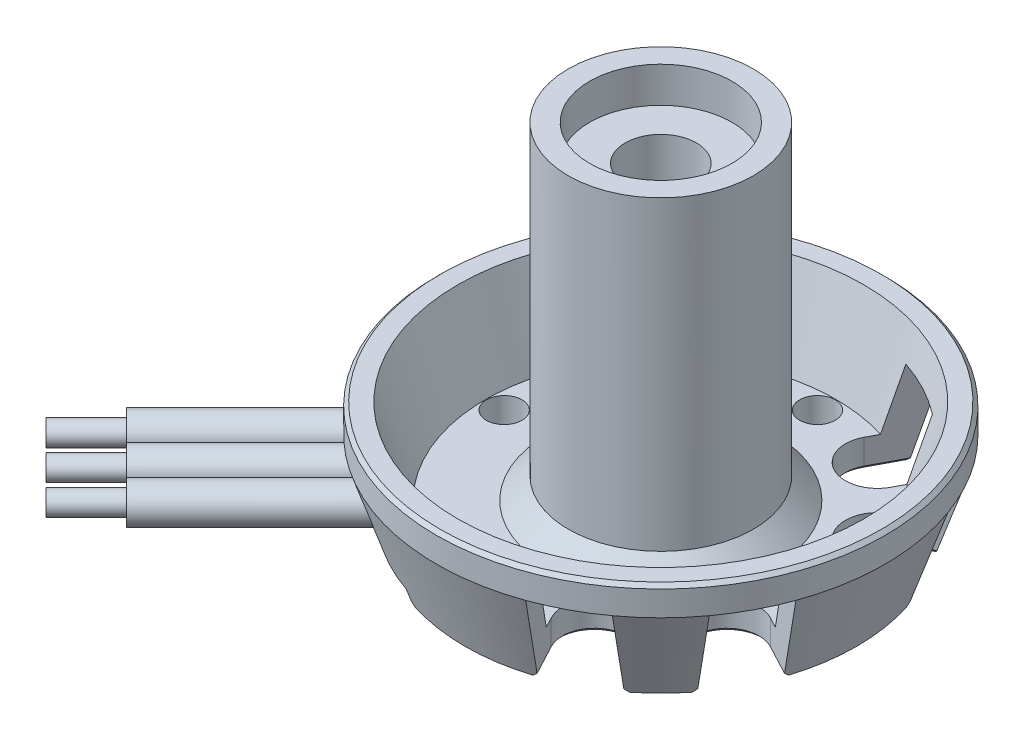
SolidWorks part; units mm, degrees
material "7075-T6，板材(SS)"
ref_plane "前视基准面" through (0, 0, 0) normal (0, 0, 1) x (1, 0, 0)
ref_plane "上视基准面" through (0, 0, 0) normal (0, 1, 0) x (1, 0, 0)
ref_plane "右视基准面" through (0, 0, 0) normal (1, 0, 0) x (0, 0, -1)
sketch "草图3" plane through (0, 0, 0) normal (0, 1, 0) x (1, 0, 0)
  circle A0 centre (0, 0) radius 31.5
  dimension "D1" = 63
extrude "凸台-拉伸1" add sketch "草图3" along normal blind 81
sketch "草图4" plane through (0, 0, 0) normal (0, -1, 0) x (1, 0, 0)
  line L0 (0, 0) -> (31.5, 0) construction
  line L1 (10.5631, 19.8663) -> (0, 0) construction
  line L2 (0, 0) -> (0, 31.5) construction
  line L3 (0, 0) -> (22.2739, 22.2739) construction
  line L4 (10.5631, 19.8663) -> (14.7884, 27.8128) construction
  line L5 (6.5898, 21.9789) -> (10.8151, 29.9255)
  line L6 (14.5364, 17.7537) -> (18.7616, 25.7002)
  line L7 (19.8663, 10.5631) -> (27.8128, 14.7884) construction
  line L8 (21.9789, 6.5898) -> (29.9255, 10.8151)
  line L9 (17.7537, 14.5364) -> (25.7002, 18.7616)
  line L10 (-10.5631, 19.8663) -> (-14.7884, 27.8128) construction
  line L11 (-6.5898, 21.9789) -> (-10.8151, 29.9255)
  line L12 (-14.5364, 17.7537) -> (-18.7616, 25.7002)
  line L13 (-19.8663, 10.5631) -> (-27.8128, 14.7884) construction
  line L14 (-21.9789, 6.5898) -> (-29.9255, 10.8151)
  line L15 (-17.7537, 14.5364) -> (-25.7002, 18.7616)
  line L16 (10.5631, -19.8663) -> (14.7884, -27.8128) construction
  line L17 (6.5898, -21.9789) -> (10.8151, -29.9255)
  line L18 (14.5364, -17.7537) -> (18.7616, -25.7002)
  line L19 (19.8663, -10.5631) -> (27.8128, -14.7884) construction
  line L20 (21.9789, -6.5898) -> (29.9255, -10.8151)
  line L21 (17.7537, -14.5364) -> (25.7002, -18.7616)
  line L22 (-10.5631, -19.8663) -> (-14.7884, -27.8128) construction
  line L23 (-6.5898, -21.9789) -> (-10.8151, -29.9255)
  line L24 (-14.5364, -17.7537) -> (-18.7616, -25.7002)
  line L25 (-19.8663, -10.5631) -> (-27.8128, -14.7884) construction
  line L26 (-21.9789, -6.5898) -> (-29.9255, -10.8151)
  line L27 (-17.7537, -14.5364) -> (-25.7002, -18.7616)
  circle A0 centre (0, 0) radius 22 construction
  arc A1 (21.9789, 6.5898) -> (17.7537, 14.5364) centre (19.8663, 10.5631) cw
  circle A2 centre (0, 0) radius 31.5 construction
  arc A3 (25.7002, 18.7616) -> (29.9255, 10.8151) centre (27.8128, 14.7884) cw
  arc A4 (6.5898, 21.9789) -> (14.5364, 17.7537) centre (10.5631, 19.8663) ccw
  arc A5 (18.7616, 25.7002) -> (10.8151, 29.9255) centre (14.7884, 27.8128) ccw
  arc A6 (-6.5898, 21.9789) -> (-14.5364, 17.7537) centre (-10.5631, 19.8663) cw
  arc A7 (-18.7616, 25.7002) -> (-10.8151, 29.9255) centre (-14.7884, 27.8128) cw
  arc A8 (-21.9789, 6.5898) -> (-17.7537, 14.5364) centre (-19.8663, 10.5631) ccw
  arc A9 (-25.7002, 18.7616) -> (-29.9255, 10.8151) centre (-27.8128, 14.7884) ccw
  arc A10 (6.5898, -21.9789) -> (14.5364, -17.7537) centre (10.5631, -19.8663) cw
  arc A11 (18.7616, -25.7002) -> (10.8151, -29.9255) centre (14.7884, -27.8128) cw
  arc A12 (21.9789, -6.5898) -> (17.7537, -14.5364) centre (19.8663, -10.5631) ccw
  arc A13 (25.7002, -18.7616) -> (29.9255, -10.8151) centre (27.8128, -14.7884) ccw
  arc A14 (-6.5898, -21.9789) -> (-14.5364, -17.7537) centre (-10.5631, -19.8663) ccw
  arc A15 (-18.7616, -25.7002) -> (-10.8151, -29.9255) centre (-14.7884, -27.8128) ccw
  arc A16 (-21.9789, -6.5898) -> (-17.7537, -14.5364) centre (-19.8663, -10.5631) cw
  arc A17 (-25.7002, -18.7616) -> (-29.9255, -10.8151) centre (-27.8128, -14.7884) cw
  circle A18 centre (0, 22) radius 2.5
  circle A19 centre (0, -22) radius 2.5
  circle A20 centre (-22, 0) radius 2.5
  circle A21 centre (22, 0) radius 2.5
  point P13 (12.6757, 23.8396)
  point P19 (23.8396, 12.6757)
  point P26 (-12.6757, 23.8396)
  point P33 (-23.8396, 12.6757)
  point P40 (12.6757, -23.8396)
  point P47 (23.8396, -12.6757)
  point P54 (-12.6757, -23.8396)
  point P61 (-23.8396, -12.6757)
  dimension "D1" = 44
  dimension "D2" = 22.5
  dimension "D6" = 5
  dimension "D3" = 28
  dimension "D4" = 9
  dimension "D5" = 45
extrude "切除-拉伸1" cut sketch "草图4" against normal blind 2
sketch "草图5" plane through (0, 0, 0) normal (0, -1, 0) x (1, 0, 0)
  circle A0 centre (0, 0) radius 9
  dimension "D1" = 18
extrude "切除-拉伸2" cut sketch "草图5" against normal blind 1.2
sketch "草图6" plane through (0, 1.2, 0) normal (0, -1, 0) x (1, 0, 0)
  circle A0 centre (0, 0) radius 5
  dimension "D1" = 10
extrude "凸台-拉伸2" add sketch "草图6" along normal blind 40
ref_plane "基准面1" through (-9.2322, 0, 9.2322) normal (-0.7071, 0, 0.7071) x (0.7071, 0, 0.7071)
sketch "草图9" plane through (0, 0, 0) normal (1, 0, 0) x (0, 0, -1)
  line L0 (-31.5, 0) -> (-31.5, -3.75)
  line L1 (-31.5, 81) -> (-31.5, 0) construction
  line L2 (-31.5, -3.75) -> (-35.25, 0)
  line L3 (-25.415, 0) -> (-18.6099, 0) construction
  line L4 (-35.25, 0) -> (-31.5, 0)
  line L5 (0, 0) -> (0, 10.6937) construction
  line L6 (-31.5, 81) -> (-31.5, 0) construction
  line L7 (-31.5, 16.5) -> (-30.5, 16.5)
  line L8 (-31.5, 16.5) -> (-31.5, 16)
  line L9 (-31.5, 16) -> (-30.5, 16)
  line L10 (-30.5, 16.5) -> (-30.5, 16)
  line L11 (-31.5, 81) -> (-31.5, 0) construction
  dimension "D1" = 45
  dimension "D2" = 35.25
  dimension "D3" = 0.5
  dimension "D4" = 16
  dimension "D5" = 1
revolve "切除-旋转1" cut sketch "草图9" angle 360 about L5
chamfer "倒角1" distance 1.2 angle 45 1 edges at (0, 1.2, -9)
sketch "草图11" plane through (0, 2, 0) normal (0, -1, 0) x (1, 0, 0)
  line L0 (14.5364, 17.7537) -> (18.6099, 25.415) construction
  line L1 (10.6634, 29.6402) -> (6.5898, 21.9789) construction
  line L2 (25.415, 18.6099) -> (17.7537, 14.5364) construction
  line L3 (21.9789, 6.5898) -> (29.6402, 10.6634) construction
  line L4 (17.7537, -14.5364) -> (25.415, -18.6099) construction
  line L5 (29.6402, -10.6634) -> (21.9789, -6.5898) construction
  line L6 (18.6099, -25.415) -> (14.5364, -17.7537) construction
  line L7 (6.5898, -21.9789) -> (10.6634, -29.6402) construction
  line L8 (-14.5364, -17.7537) -> (-18.6099, -25.415) construction
  line L9 (-10.6634, -29.6402) -> (-6.5898, -21.9789) construction
  line L10 (-25.415, -18.6099) -> (-17.7537, -14.5364) construction
  line L11 (-21.9789, -6.5898) -> (-29.6402, -10.6634) construction
  line L12 (14.5364, 17.7537) -> (22.5148, 32.7589)
  line L13 (14.5683, 36.9842) -> (6.5898, 21.9789)
  line L14 (32.7589, 22.5148) -> (17.7537, 14.5364)
  line L15 (21.9789, 6.5898) -> (36.9842, 14.5683)
  line L16 (17.7537, -14.5364) -> (32.7589, -22.5148)
  line L17 (36.9842, -14.5683) -> (21.9789, -6.5898)
  line L18 (22.5148, -32.7589) -> (14.5364, -17.7537)
  line L19 (6.5898, -21.9789) -> (14.5683, -36.9842)
  line L20 (-14.5364, -17.7537) -> (-22.5148, -32.7589)
  line L21 (-14.5683, -36.9842) -> (-6.5898, -21.9789)
  line L22 (-32.7589, -22.5148) -> (-17.7537, -14.5364)
  line L23 (-21.9789, -6.5898) -> (-36.9842, -14.5683)
  arc A1 (6.5898, 21.9789) -> (14.5364, 17.7537) centre (10.5631, 19.8663) ccw construction
  arc A3 (17.7537, 14.5364) -> (21.9789, 6.5898) centre (19.8663, 10.5631) ccw construction
  arc A5 (21.9789, -6.5898) -> (17.7537, -14.5364) centre (19.8663, -10.5631) ccw construction
  arc A7 (14.5364, -17.7537) -> (6.5898, -21.9789) centre (10.5631, -19.8663) ccw construction
  arc A9 (-6.5898, -21.9789) -> (-14.5364, -17.7537) centre (-10.5631, -19.8663) ccw construction
  arc A11 (-17.7537, -14.5364) -> (-21.9789, -6.5898) centre (-19.8663, -10.5631) ccw construction
  circle A12 centre (22, 0) radius 2.5 construction
  arc A13 (6.5898, 21.9789) -> (14.5364, 17.7537) centre (10.5631, 19.8663) ccw
  circle A14 centre (0, -22) radius 2.5 construction
  arc A15 (17.7537, 14.5364) -> (21.9789, 6.5898) centre (19.8663, 10.5631) ccw
  circle A16 centre (-22, 0) radius 2.5 construction
  arc A17 (21.9789, -6.5898) -> (17.7537, -14.5364) centre (19.8663, -10.5631) ccw
  circle A18 centre (0, 22) radius 2.5 construction
  arc A19 (14.5364, -17.7537) -> (6.5898, -21.9789) centre (10.5631, -19.8663) ccw
  circle A20 centre (22, 0) radius 2.5
  arc A21 (-6.5898, -21.9789) -> (-14.5364, -17.7537) centre (-10.5631, -19.8663) ccw
  circle A22 centre (0, -22) radius 2.5
  arc A23 (-17.7537, -14.5364) -> (-21.9789, -6.5898) centre (-19.8663, -10.5631) ccw
  arc A25 (-36.9842, -14.5683) -> (-32.7589, -22.5148) centre (0, 0) ccw
  arc A26 (-22.5148, -32.7589) -> (-14.5683, -36.9842) centre (0, 0) ccw
  arc A27 (14.5683, -36.9842) -> (22.5148, -32.7589) centre (0, 0) ccw
  arc A28 (32.7589, -22.5148) -> (36.9842, -14.5683) centre (0, 0) ccw
  arc A29 (36.9842, 14.5683) -> (32.7589, 22.5148) centre (0, 0) ccw
  arc A30 (22.5148, 32.7589) -> (14.5683, 36.9842) centre (0, 0) ccw
  circle A31 centre (-22, 0) radius 2.5
  circle A32 centre (0, 22) radius 2.5
  dimension "D1" = 39.75
extrude "切除-拉伸3" cut sketch "草图11" against normal offset from surface (10 mm away) 12 up to face at (0, 0, -9)
sketch "Sketch2" plane through (0, 0, 0) normal (0, 0, 1) x (1, 0, 0)
  line L0 (31.5, 12) -> (31.5, 0)
  line L2 (31.5, 0) -> (27.5, 0)
  line L3 (21.9789, 0) -> (29.6402, 0) construction
  line L4 (27.5, 0) -> (31.5, 12)
  line L5 (25.415, 12) -> (29.6402, 12) construction
  line L6 (0, 0) -> (0, -6.7384) construction
  line L7 (25.415, 12) -> (29.6402, 12) construction
  line L8 (31.5, 0) -> (31.5, 16) construction
  dimension "D1" = 4
revolve "Cut-Revolve1" cut sketch "Sketch2" angle 360 about L6
sketch "草图12" plane through (0, 16, 0) normal (0, 1, 0) x (1, 0, 0)
  circle A1 centre (0, 0) radius 31.5
  circle A2 centre (0, 0) radius 31.5
  dimension "D1" = 0
extrude "切除-拉伸4" cut sketch "草图12" along normal through all
sketch "草图13" plane through (0, -38.8, 0) normal (0, -1, 0) x (1, 0, 0)
  circle A1 centre (0, 0) radius 5
  circle A2 centre (0, 0) radius 5
  dimension "D1" = 0
extrude "切除-拉伸5" cut sketch "草图13" against normal through all
sketch "草图8" plane through (-9.2322, 0, 9.2322) normal (-0.7071, 0, 0.7071) x (0.7071, 0, 0.7071)
  line L0 (-31.5, 0) -> (28.499, 0) construction
  line L1 (0, 8) -> (0, 0) construction
  circle A0 centre (0, 8) radius 2.5
  circle A1 centre (6, 8) radius 2.5
  circle A2 centre (-6, 8) radius 2.5
  point P10 (0, 0)
  dimension "D1" = 5
  dimension "D2" = 8
  dimension "D4" = 6
  dimension "D3" = 2
extrude "凸台-拉伸3" add sketch "草图8" along normal blind 40
sketch "草图15" plane through (0, 16, 0) normal (0, 1, 0) x (1, 0, 0)
  circle A0 centre (0, 0) radius 28.5
  circle A1 centre (0, 0) radius 31.5
  circle A2 centre (0, 0) radius 31.5 construction
  dimension "D1" = 0
  dimension "D2" = 3
extrude "切除-拉伸6" cut sketch "草图15" against normal offset from surface 8 draft 18
sketch "草图16" plane through (0, 4, 0) normal (0, 1, 0) x (1, 0, 0)
  circle A0 centre (0, 0) radius 10
  circle A1 centre (0, 0) radius 13
  dimension "D1" = 20
  dimension "D2" = 26
extrude "凸台-拉伸4" add sketch "草图16" along normal offset from surface (46 mm away) 50 up to face at (0, 0, -9)
chamfer "倒角2" distance 3 angle 45 1 edges at (0, 4, 13)
sketch "草图21" plane through (0, 50, 0) normal (0, 1, 0) x (1, 0, 0)
  circle A0 centre (0, 0) radius 5
  circle A1 centre (0, 0) radius 10 construction
  circle A2 centre (0, 0) radius 10
  dimension "D1" = 10
extrude "凸台-拉伸7" add sketch "草图21" along normal blind 10 from offset 15 offset against normal yes
sketch "草图22" plane through (-37.5165, 0, 37.5165) normal (-0.7071, 0, 0.7071) x (0.7071, 0, 0.7071)
  circle A0 centre (6, 8) radius 2.5 construction
  circle A1 centre (0, 8) radius 2.5 construction
  circle A2 centre (-6, 8) radius 2.5 construction
  circle A3 centre (6, 8) radius 2.5 construction
  circle A4 centre (0, 8) radius 2.5 construction
  circle A5 centre (-6, 8) radius 2.5 construction
  circle A6 centre (6, 8) radius 1.5
  circle A7 centre (0, 8) radius 1.5
  circle A8 centre (-6, 8) radius 1.5
  dimension "D1" = 1
extrude "凸台-拉伸8" add sketch "草图22" along normal blind 8
chamfer "倒角4" distance 0.5 angle 45 32 edges at (15.8931, 0, -8.4505) (8.4505, 0, -15.8931) (7.6765, 0, -24.0227) (15.623, 0, -19.7974) (24.0227, 0, -7.6765) (-24.0227, 0, 7.6765) (-15.623, 0, 19.7974) (19.7974, 0, 15.623) (-7.6765, 0, -24.0227) (-19.7974, 0, -15.623) (-15.8931, 0, -8.4505) (-24.0227, 0, -7.6765) (-15.623, 0, -19.7974) (-8.4505, 0, -15.8931) (7.6765, 0, 24.0227) (15.8931, 0, 8.4505) (24.0227, 0, 7.6765) (-8.4505, 0, 15.8931) (-7.6765, 0, 24.0227) (15.623, 0, 19.7974) (-19.7974, 0, 15.623) (-15.8931, 0, 8.4505) (8.4505, 0, 15.8931) (19.7974, 0, -15.623)
chamfer "Chamfer1" distance 0.5 angle 45 1 edges at (0, 16, -31.5)
